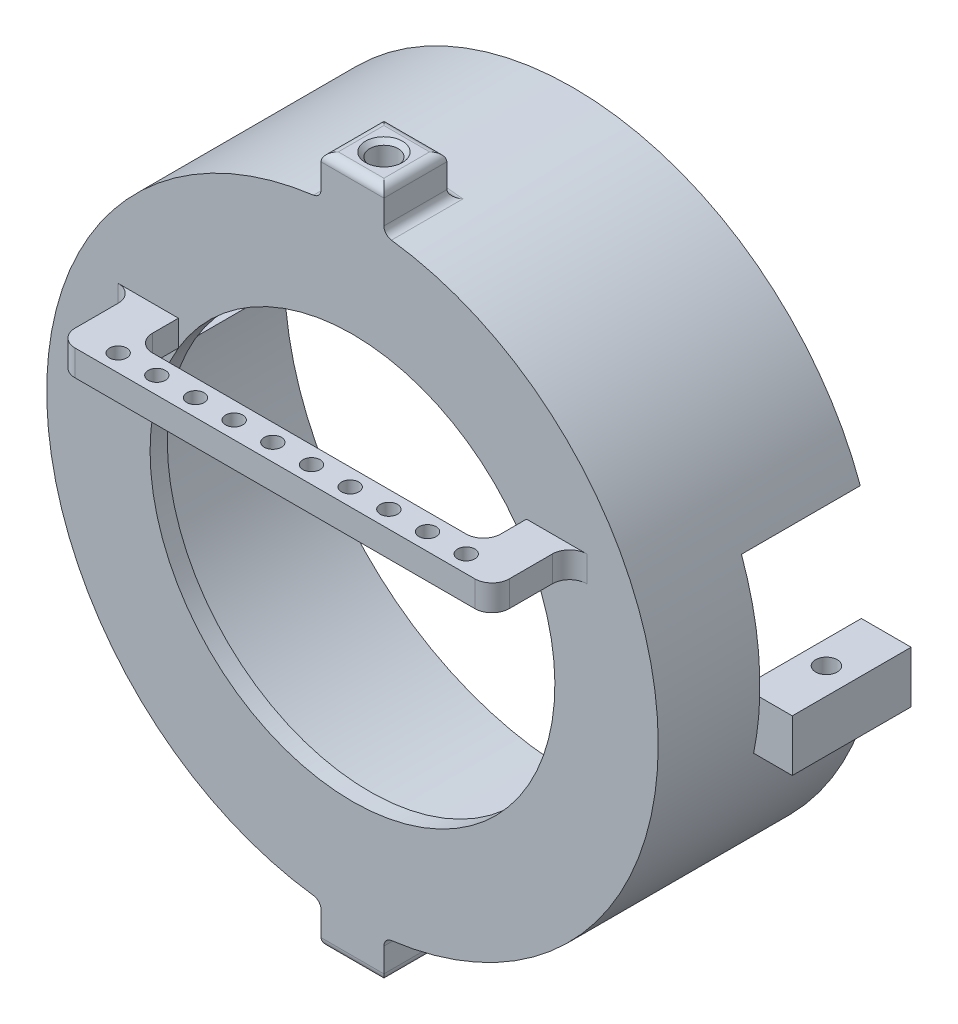
SolidWorks part; units mm, degrees
note: The reader was unsure of these and kept them because the rebuilt part matched: shared geometry of "Sketch6<3>", "Sketch12<5>", "Sketch12<7>".
ref_plane "Front Plane" through (0, 0, 0) normal (1, 0, 0) x (0, 1, 0)
ref_plane "Top Plane" through (0, 0, 0) normal (0, 0, 1) x (0, 1, 0)
ref_plane "Right Plane" through (0, 0, 0) normal (0, 1, 0) x (-1, 0, 0)
sketch "Sketch3" plane through (0, 0, 0) normal (1, 0, 0) x (0, 1, 0)
  line L1 (23.5, 0) -> (33.5, 0)
  line L2 (33.5, 0) -> (33.5, -23.6)
  line L3 (33.5, -23.6) -> (35.5, -23.6)
  line L4 (35.5, -23.6) -> (35.5, 2)
  line L5 (35.5, 2) -> (23.5, 2)
  line L6 (23.5, 2) -> (23.5, 0)
  line L7 (0, 0) -> (0, 29.6776) construction
  dimension "D1" = 67
  dimension "D2" = 2
  dimension "D3" = 2
  dimension "D4" = 23.6
  dimension "D5" = 10
revolve "Revolve1" add sketch "Sketch3" angle 360 about L7
sketch "Sketch6" plane through (0, 0, 0) normal (1, 0, 0) x (0, 1, 0)
  line L0 (-35.5, -23.6) -> (35.5, -23.6) construction
  line L6 (-1.15, -9.8) -> (1.15, -9.8)
  line L7 (-1.15, -9.8) -> (-1.15, -23.6)
  line L8 (-1.15, -23.6) -> (1.15, -23.6)
  line L9 (1.15, -9.8) -> (1.15, -23.6)
  line L10 (-1.15, -9.8) -> (-7.15, -9.8)
  line L11 (-1.15, -9.8) -> (-1.15, -23.6)
  line L12 (-1.15, -23.6) -> (-7.15, -23.6)
  line L13 (-7.15, -9.8) -> (-7.15, -23.6)
  point P6 (0, -9.8)
  dimension "D1" = 13.8
  dimension "D2" = 2.3
  dimension "D3" = 6
extrude "Boss-Extrude1" add sketch "Sketch6" against normal up to surface (3.7786 mm away) from offset 39.26 contours L10 L13 L12 L7
mirror "Mirror1" about plane through (0, 0, 0) normal (1, 0, 0) of "Boss-Extrude1"
extrude "Cut-Extrude2" cut sketch "Sketch6<3>" against normal through all both and the other way through all contours L9 L6 L7 L8
sketch "Sketch6<3>" plane through (0, 0, 0) normal (1, 0, 0) x (0, 1, 0) same geometry as "Sketch6"
sketch "Sketch11" plane through (0, -1.15, 0) normal (0, 1, 0) x (-1, 0, 0)
  line L0 (-33.4803, -23.6) -> (-39.26, -23.6) construction
  line L1 (-39.26, -9.8) -> (-39.26, -23.6) construction
  circle A0 centre (-36.2199, -16.8054) radius 1.25
  dimension "D2" = 2.5
  dimension "D1" = 6.7946
  dimension "D3" = 3.0401
extrude "Cut-Extrude5" cut sketch "Sketch11" against normal through all
sketch "Sketch12" plane through (0, 0, 0) normal (0, 1, 0) x (-1, 0, 0)
  line L1 (-3.651, 2) -> (3.651, 2)
  line L2 (-3.651, 2) -> (-3.651, -5.302)
  line L3 (-3.651, -5.302) -> (3.651, -5.302)
  line L4 (3.651, 2) -> (3.651, -5.302)
  line L5 (-3.651, -5.302) -> (3.651, 2) construction
  line L6 (35.5, 2) -> (-35.5, 2) construction
  circle A0 centre (0, -1.651) radius 1.651
  point P4 (-2.9467, -6.983)
  point P5 (0, 0)
  point P6 (0, 0)
  dimension "D1" = 3.302
  dimension "D2" = 2
extrude "Boss-Extrude4" add sketch "Sketch12" against normal up to surface (4.6882 mm away) from offset 40 contours L2 L5 A0 L1 | A0 L5 | L5 A0 | L5 L3 L4 A0
extrude "Boss-Extrude5" add sketch "Sketch12<5>" along normal up to surface (4.6882 mm away) from offset 40 contours A0 L5 | L5 A0 | L2 L5 A0 L1 | L5 L3 L4 A0 offset against normal yes
sketch "Sketch12<5>" plane through (0, 0, 0) normal (0, 1, 0) x (-1, 0, 0) same geometry as "Sketch12"
extrude "Cut-Extrude6" cut sketch "Sketch12<7>" against normal through all both and the other way through all contours L5 A0 | A0 L5
sketch "Sketch12<7>" plane through (0, 0, 0) normal (0, 1, 0) x (-1, 0, 0) same geometry as "Sketch12"
fillet "Fillet2" radius 1 14 edges at (0, 40, 2) (3.651, -35.3118, -1.651) (3.651, -40, -1.651) (0, -40, -5.302) (0, -40, 2) (0, -35.5, -5.302) (-3.651, -35.3118, -1.651) (-3.651, -40, -1.651) (0, 40, -5.302) (0, 35.5, -5.302) (3.651, 40, -1.651) (3.651, 35.3118, -1.651) (-3.651, 40, -1.651) (-3.651, 35.3118, -1.651)
chamfer "Chamfer2" distance 0.5 angle 45 2 edges at (0, 40, 0) (0, -40, 0)
sketch "Sketch9" plane through (0, 0, 0) normal (0, 1, 0) x (-1, 0, 0)
  line L0 (-33.4803, -9.8) -> (-35.4814, -9.8) construction
  line L1 (-33.4803, -9.8) -> (-36.4803, -9.8)
  line L2 (-33.4803, -9.8) -> (-33.4803, -23.6)
  line L3 (-33.4803, -23.6) -> (-36.4803, -23.6)
  line L4 (-36.4803, -9.8) -> (-36.4803, -23.6)
  line L5 (-33.4803, -23.6) -> (-33.4803, -9.8) construction
  line L6 (-33.4803, -23.6) -> (-39.26, -23.6) construction
  line L7 (0, 0) -> (0, -37.5101) construction
  dimension "D1" = 3
revolve "Cut-Revolve1" cut sketch "Sketch9" angle 20 about L7
mirror "Mirror9" about plane through (0, 0, 0) normal (1, 0, 0) of "Cut-Extrude5", "Cut-Revolve1"
ref_plane "Plane1" through (0, 12, 0) normal (0, 1, 0) x (-1, 0, 0)
sketch "Sketch13" plane through (0, 12, 0) normal (0, 1, 0) x (-1, 0, 0)
  line L0 (23.5, 2) -> (-23.5, 2) construction
  line L1 (-25.2052, 2) -> (-20.2052, 2)
  line L2 (-25.2052, 2) -> (-25.2052, 11)
  line L4 (-20.2052, 2) -> (-20.2052, 7)
  line L5 (-25.2052, 11) -> (25.2052, 11)
  line L6 (25.2052, 11) -> (25.2052, 2)
  line L7 (25.2052, 2) -> (20.2052, 2)
  line L8 (20.2052, 2) -> (20.2052, 7)
  line L9 (20.2052, 7) -> (-20.2052, 7)
  line L10 (-20.2052, 9) -> (-15.7152, 9) construction
  line L15 (-20.2052, 7) -> (-20.2052, 11) construction
  line L16 (-20.2052, 9) -> (20.2052, 9) construction
  line L17 (20.2052, 11) -> (20.2052, 7) construction
  circle A2 centre (-20.2052, 9) radius 1
  circle A3 centre (-15.7152, 9) radius 1
  circle A4 centre (-11.2251, 9) radius 1
  circle A5 centre (-6.7351, 9) radius 1
  circle A6 centre (-2.245, 9) radius 1
  circle A7 centre (2.245, 9) radius 1
  circle A8 centre (6.7351, 9) radius 1
  circle A9 centre (11.2251, 9) radius 1
  circle A10 centre (15.7152, 9) radius 1
  circle A11 centre (20.2052, 9) radius 1
  dimension "D1" = 5
  dimension "D2" = 4
  dimension "D4" = 2
  dimension "D3" = 5
  dimension "D6" = 4.49
  dimension "D5" = 10
extrude "Boss-Extrude6" add sketch "Sketch13" along normal blind 3
fillet "Fillet3" radius 2 6 edges at (25.2052, 13.5, 2) (25.2052, 13.5, 11) (20.2052, 13.5, 7) (-20.2052, 13.5, 7) (-25.2052, 13.5, 11) (-25.2052, 13.5, 2)
